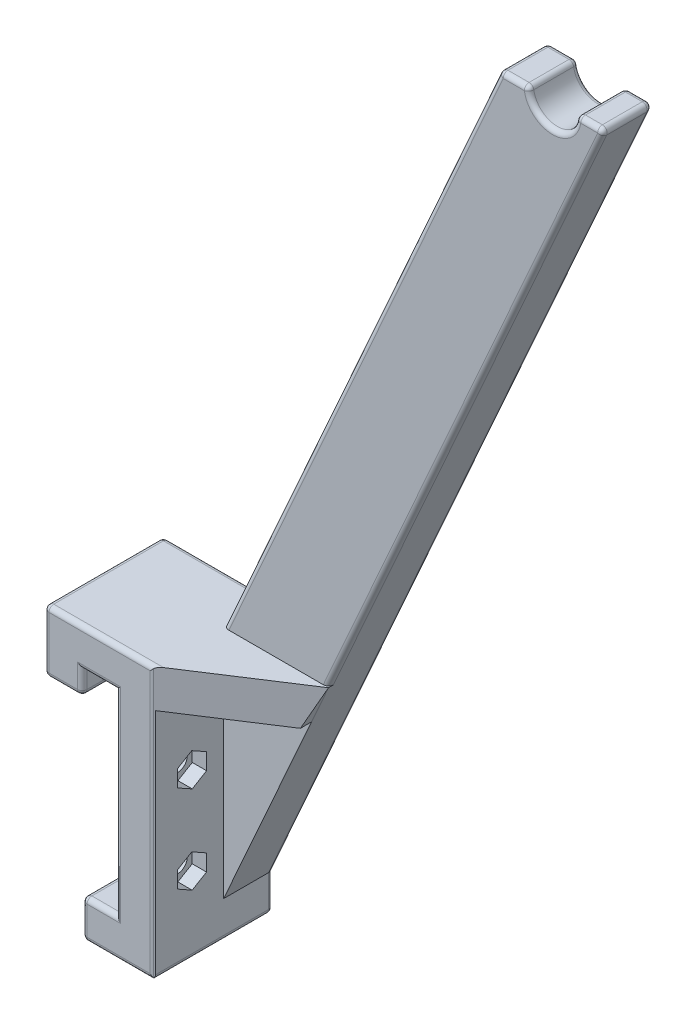
SolidWorks part; units mm, degrees
ref_plane "Спереди" through (0, 0, 0) normal (0, 0, 1) x (1, 0, 0)
ref_plane "Сверху" through (0, 0, 0) normal (0, 1, 0) x (1, 0, 0)
ref_plane "Справа" through (0, 0, 0) normal (1, 0, 0) x (0, 0, -1)
sketch "Эскиз1" plane through (0, 0, 0) normal (0, 0, 1) x (1, 0, 0)
  line L1 (0, 0) -> (8, 0)
  line L2 (0, 0) -> (0, -57)
  line L3 (0, -57) -> (8, -57)
  line L4 (8, 0) -> (8, -57)
  dimension "D1" = 8
  dimension "D2" = 57
extrude "Бобышка-Вытянуть1" add sketch "Эскиз1" along normal blind 25
sketch "Эскиз2" plane through (0, 0, 0) normal (-1, 0, 0) x (0, 0, 1)
  line L0 (25, 0) -> (25, -57) construction
  line L1 (0, 0) -> (25, 0)
  line L2 (0, 0) -> (0, -8)
  line L3 (0, -8) -> (25, -8)
  line L4 (25, 0) -> (25, -8)
  dimension "D1" = 8
extrude "Бобышка-Вытянуть2" add sketch "Эскиз2" along normal blind 15
sketch "Эскиз3" plane through (0, 0, 0) normal (-1, 0, 0) x (0, 0, 1)
  line L0 (25, -8) -> (25, -57) construction
  line L1 (0, -57) -> (25, -57)
  line L2 (0, -57) -> (0, -49)
  line L3 (0, -49) -> (25, -49)
  line L4 (25, -57) -> (25, -49)
  dimension "D1" = 8
extrude "Бобышка-Вытянуть3" add sketch "Эскиз3" along normal blind 7
sketch "Эскиз4" plane through (0, -8, 0) normal (0, -1, 0) x (1, 0, 0)
  line L0 (-15, 0) -> (0, 0) construction
  line L1 (-15, 25) -> (-7, 25)
  line L2 (-15, 25) -> (-15, 0)
  line L3 (-15, 0) -> (-7, 0)
  line L4 (-7, 25) -> (-7, 0)
  dimension "D1" = 8
extrude "Бобышка-Вытянуть4" add sketch "Эскиз4" along normal blind 5
sketch "Эскиз5" plane through (0, 0, 0) normal (-1, 0, 0) x (0, 0, 1)
  line L0 (17, -28.5) -> (17, 8.7834) construction
  line L1 (25, -8) -> (25, -49) construction
  line L2 (17, -28.5) -> (17, -61.0126) construction
  circle A0 centre (17, -22.5896) radius 2
  circle A1 centre (17, -40.9756) radius 2
  dimension "D1" = 8
extrude "Вырез-Вытянуть1" cut sketch "Эскиз5" against normal through all
sketch "Эскиз6" plane through (8, 0, 0) normal (1, 0, 0) x (0, 0, -1)
  line L1 (-13.9411, -24.2905) -> (-13.9975, -20.7909)
  line L2 (-13.9975, -20.7909) -> (-17.0564, -19.09)
  line L3 (-17.0564, -19.09) -> (-20.0589, -20.8887)
  line L4 (-20.0589, -20.8887) -> (-20.0025, -24.3882)
  line L5 (-20.0025, -24.3882) -> (-16.9436, -26.0891)
  line L6 (-16.9436, -26.0891) -> (-13.9411, -24.2905)
  line L13 (-13.9509, -42.6941) -> (-13.9872, -39.1943)
  line L14 (-13.9872, -39.1943) -> (-17.0363, -37.4758)
  line L15 (-17.0363, -37.4758) -> (-20.0491, -39.2571)
  line L16 (-20.0491, -39.2571) -> (-20.0128, -42.7569)
  line L17 (-20.0128, -42.7569) -> (-16.9637, -44.4754)
  line L18 (-16.9637, -44.4754) -> (-13.9509, -42.6941)
  circle A0 centre (-17, -22.5896) radius 3.5 construction
  circle A1 centre (-17, -40.9756) radius 3.5 construction
extrude "Вырез-Вытянуть2" cut sketch "Эскиз6" against normal blind 3
sketch "Эскиз7" plane through (8, 0, 0) normal (1, 0, 0) x (0, 0, -1)
  line L0 (-25, -57) -> (0, -57) construction
  line L1 (0, 0) -> (-10.3631, 0)
  line L2 (0, 0) -> (0, -57)
  line L3 (0, -57) -> (-10.3631, -57)
  line L4 (-10.3631, 0) -> (-10.3631, -57)
extrude "Бобышка-Вытянуть5" add sketch "Эскиз7" along normal blind 80
sketch "Эскиз8" plane through (0, 0, 0) normal (0, 1, 0) x (1, 0, 0)
  line L1 (88, 0) -> (8, 0)
  line L2 (88, 0) -> (88, -10.3631)
  line L3 (88, -10.3631) -> (8, -10.3631)
  line L4 (8, 0) -> (8, -10.3631)
extrude "Бобышка-Вытянуть6" add sketch "Эскиз8" along normal blind 130
sketch "Эскиз9" plane through (0, 0, 10.3631) normal (0, 0, 1) x (1, 0, 0)
  line L0 (8, 130) -> (88, 130) construction
  line L1 (88, 130) -> (88, -57) construction
  line L2 (66.0002, 130) -> (8, 0)
  line L3 (8, 130) -> (8, 0) construction
  line L4 (8, 0) -> (8, 130)
  line L5 (8, 130) -> (66.0002, 130)
  line L6 (88, 130) -> (4.569, -57)
  line L7 (88, -57) -> (8, -57) construction
  line L8 (4.569, -57) -> (88, -57)
  line L9 (88, -57) -> (88, 130)
  arc A0 (82, 130) -> (72.0002, 130) centre (77.0001, 129.9712) cw
  line M2 (8, -57) -> (88, -57)
  line M3 (88, -57) -> (88, 130)
  line M4 (88, 130) -> (8, 130)
  line M5 (8, 130) -> (8, 0)
  dimension "D1" = 5
  dimension "D2" = 6
  dimension "D3" = 6
extrude "Вырез-Вытянуть3" cut sketch "Эскиз9" against normal through all contours L6 M3 M2 | L2 M4 M5 | A0 M4
sketch "Эскиз11" plane through (8, 0, 0) normal (1, 0, 0) x (0, 0, -1)
  line L0 (-10.3631, 0) -> (-10.3631, -49.3098) construction
  line L1 (-25, 0) -> (-10.3631, 0)
  line L2 (-25, 0) -> (-25, -8)
  line L3 (-25, -8) -> (-10.3631, -8)
  line L4 (-10.3631, 0) -> (-10.3631, -8)
  dimension "D1" = 8
extrude "Бобышка-Вытянуть7" add sketch "Эскиз11" along normal blind 22
sketch "Эскиз12" plane through (0, 0, 10.3631) normal (0, 0, -1) x (-1, 0, 0)
  line L0 (-30, -8) -> (-30, 0)
  line L1 (-30, 0) -> (-26.4306, -8)
  line L2 (-26.4306, -8) -> (-30, -8)
extrude "Вырез-Вытянуть4" cut sketch "Эскиз12" against normal through all
sketch "Эскиз13" plane through (0, 0, 0) normal (0, 1, 0) x (1, 0, 0)
  line L0 (30, -10.3631) -> (30, -25)
  line L1 (30, -25) -> (7.5, -25)
  line L2 (30, -25) -> (-15, -25) construction
  line L3 (7.5, -25) -> (30, -10.3631)
extrude "Вырез-Вытянуть5" cut sketch "Эскиз13" against normal through all
fillet "Скругление2" radius 1 39 edges at (85, 130, 0) (88, 130, 5.1816) (85, 130, 10.3631) (77.0001, 124.9712, 10.3631) (77.0001, 124.9712, 0) (82, 130, 5.1816) (72.0002, 130, 5.1816) (69.0002, 130, 10.3631) (66.0002, 130, 5.1816) (69.0002, 130, 0) (-15, 0, 12.5) (-15, -6.5, 25) (-15, -13, 12.5) (-15, -6.5, 0) (-3.5, 0, 0) (8, -57, 12.3374) (8, -53.1549, 0) (0.5, -57, 0) (-3.5, -49, 0) (0, -28.5, 25) (0, -28.5, 0) (-3.5, -8, 0) (-7, -10.5, 0) (-7, -13, 12.5) (-7, -53, 0) (-7, -53, 25) (0.25, -57, 25) (-7, -57, 12.5) (-7, -49, 12.5) (-3.5, -49, 25) (-3.5, -8, 25) (-7, -10.5, 25) (7.5, -28.5, 25) (-3.75, 0, 25) (-11, -13, 25) (58.9999, 65, 10.3631) (37.0001, 65, 10.3631) (37.0001, 65, 0) (48, 40.3451, 0)
